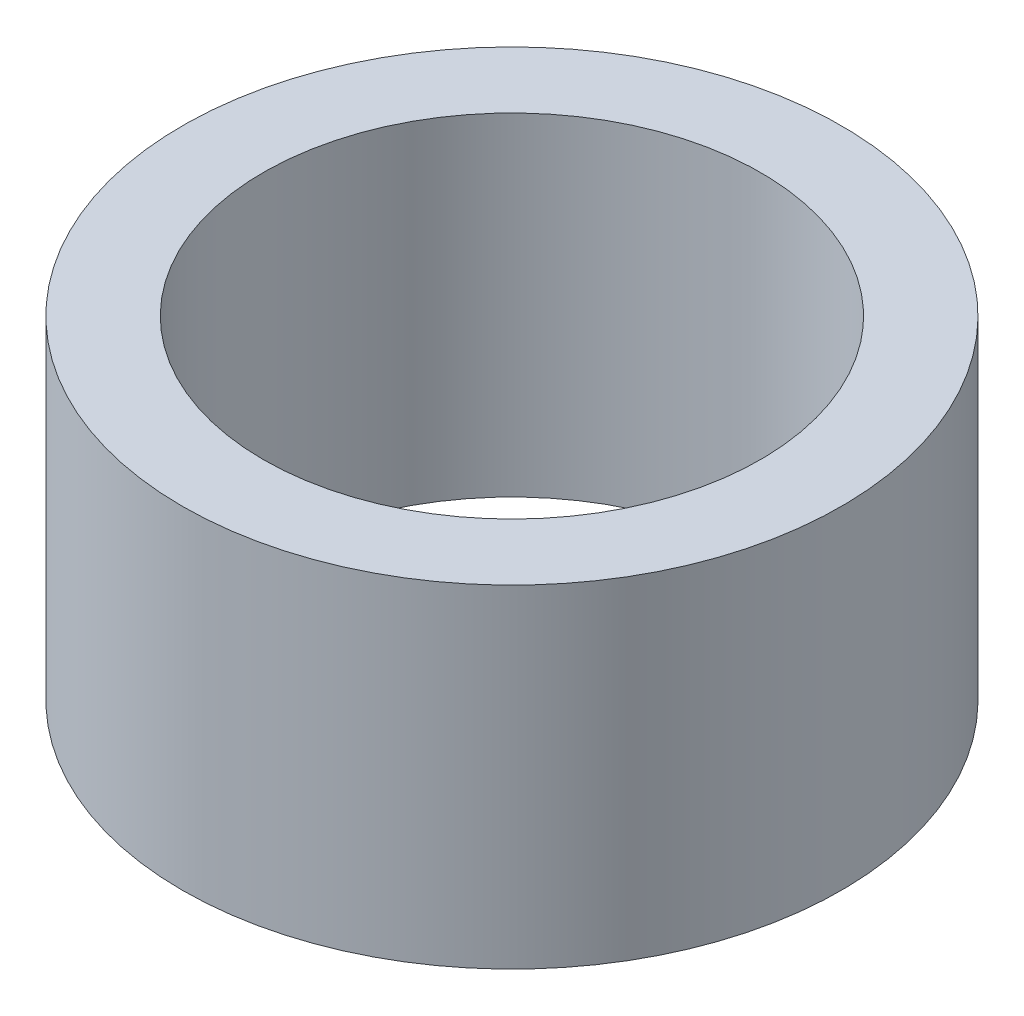
SolidWorks part; units mm, degrees
ref_plane "Front Plane" through (0, 0, 0) normal (0, 0, 1) x (1, 0, 0)
ref_plane "Top Plane" through (0, 0, 0) normal (0, 1, 0) x (1, 0, 0)
ref_plane "Right Plane" through (0, 0, 0) normal (1, 0, 0) x (0, 0, -1)
sketch "Sketch1" plane through (0, 0, 0) normal (0, 1, 0) x (1, 0, 0)
  circle A0 centre (0, 0) radius 5.5
  circle A1 centre (0, 0) radius 4.15
extrude "Boss-Extrude1" add sketch "Sketch1" along normal blind 5.55
